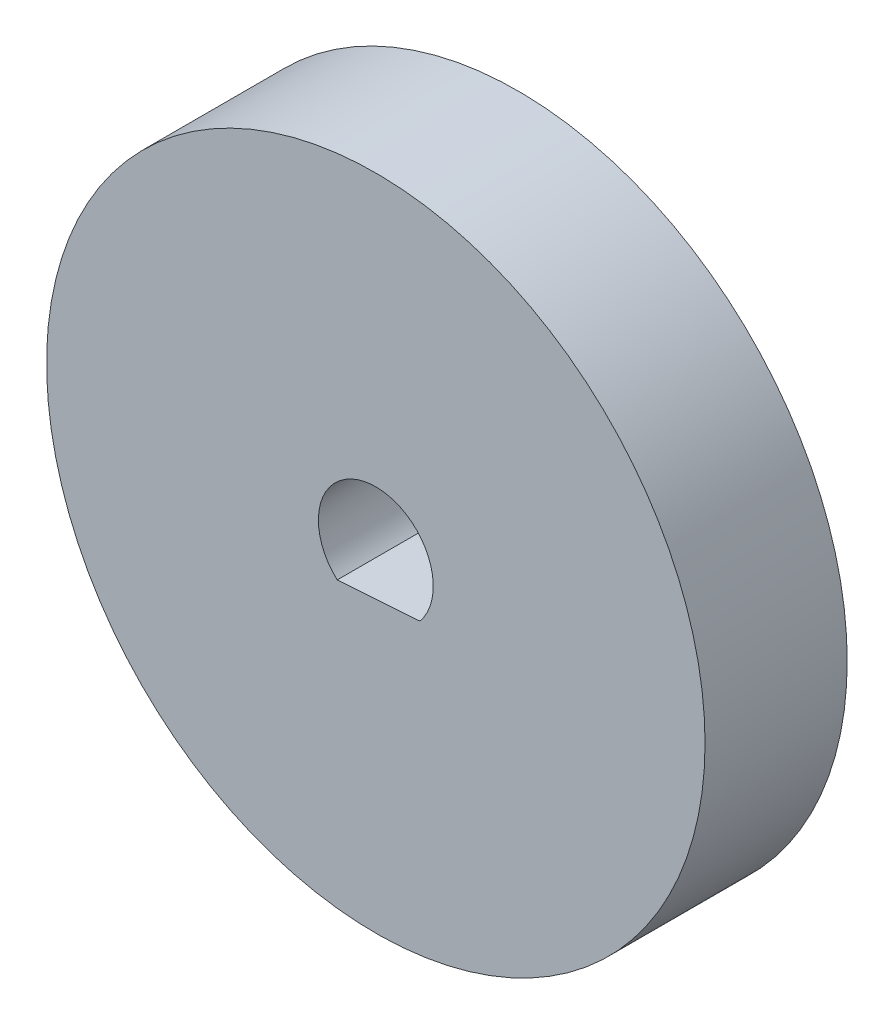
SolidWorks part; units mm, degrees
ref_plane "Front Plane" through (0, 0, 0) normal (0, 0, 1) x (1, 0, 0)
ref_plane "Top Plane" through (0, 0, 0) normal (0, 1, 0) x (1, 0, 0)
ref_plane "Right Plane" through (0, 0, 0) normal (1, 0, 0) x (0, 0, -1)
sketch "Sketch1" plane through (0, 0, 0) normal (0, 0, 1) x (1, 0, 0)
  circle A0 centre (0, 7.2896) radius 11.176
  dimension "D1" = 22.352
extrude "Boss-Extrude1" add sketch "Sketch1" along normal blind 4.826
sketch "Sketch2" plane through (0, 0, 0) normal (0, 0, -1) x (-1, 0, 0)
  line L1 (-1.4968, 6.0398) -> (1.3108, 5.8459)
  circle A0 centre (0, 7.2896) radius 1.95
  circle A1 centre (0, 7.2896) radius 11.176 construction
  dimension "D1" = 3.9
  dimension "D3" = 0
  dimension "D2" = 1.35
extrude "Cut-Extrude1" cut sketch "Sketch2" against normal through all contours L1 A0 region at (-0.0119, 7.4615, 0)
equation "\"MDF\"= 0.19in"
equation "\"Foamcore\"= .13in"
equation "\"Gmaterial\"= \"MDF\""
equation "\"D1@Boss-Extrude1\"=\"MDF\""
equation "\"PVCID\" = 2.067in"
equation "\"PVCOD\" = 2.375in"
equation "\"GenDiameter\"= 60mm"
equation "\"GenCutDiameter\" = 1.8in"
equation "\"GenCutDistance\" = 1"
equation "\"TowerHeight\" = 6in"
equation "\"TowerFrontBase\" = 3in"
equation "\"FunnelHeight\" = 1in"
equation "\"FunnelAngle\" = 20"
equation "\"TowerSideBase\" = 3in"
equation "\"TowerPanelLength\" = 2in"
equation "\"TowerPanelLeeway\" = 0.5in"
equation "\"BaseLength\" = 9in"
equation "\"BaseWidth\" = 10.5in"
equation "\"WheelHoleLength\" = 3.25in"
equation "\"WheelHoleWidth\" = 26mm"
equation "\"WheelHoleFromBack\" = 1in"
equation "\"DropLength\" = 1in"
equation "\"DropWidth\" = 8.5in"
equation "\"BumperWidth\" = 1in"
equation "\"HoleDiameter\" = 0.25in"
equation "\"SmallHexDiameter\" = 0.185in"
equation "\"SmallHexHeight\" = 0.701in"
equation "\"ScrewSize\" = 0.106in"
equation "\"BigHexDiameter\" = 0.251in"
equation "\"BigHexHeight\" = 0.374in"
equation "\"PCBThickness\" = 0.066in"
equation "\"ConnectorHeight\" = 0.517in"
equation "\"BoardHeight\" = 0.583in"
equation "\"UnoStackHeight\" = 1.351in"
equation "\"UnoStackWidth\" = 3.053in"
equation "\"UnoStackLength\" = 3.152in"
equation "\"HBridgeWidth\" = 1.797in"
equation "\"HBridgeLength\" = 2.236in"
equation "\"DSWidth\" = 1.820in"
equation "\"DSLength\" = 1.833in"
equation "\"StepperWidth\" = 1.799in"
equation "\"StepperLength\" = 2.248in"
equation "\"ULNWidth\" = 1.304in"
equation "\"ULNLength\" = 1.545in"
equation "\"VSwitchHeight\" = 0.392in"
equation "\"VSwitchWidth\" = 0.637in"
equation "\"VSwitchLength\" = 1.097in"
equation "\"SkateWheelDiameter\" = 80mm"
equation "\"SkateWheelThickness\" = 24mm"
equation "\"BaseDistance\" = 3in"
